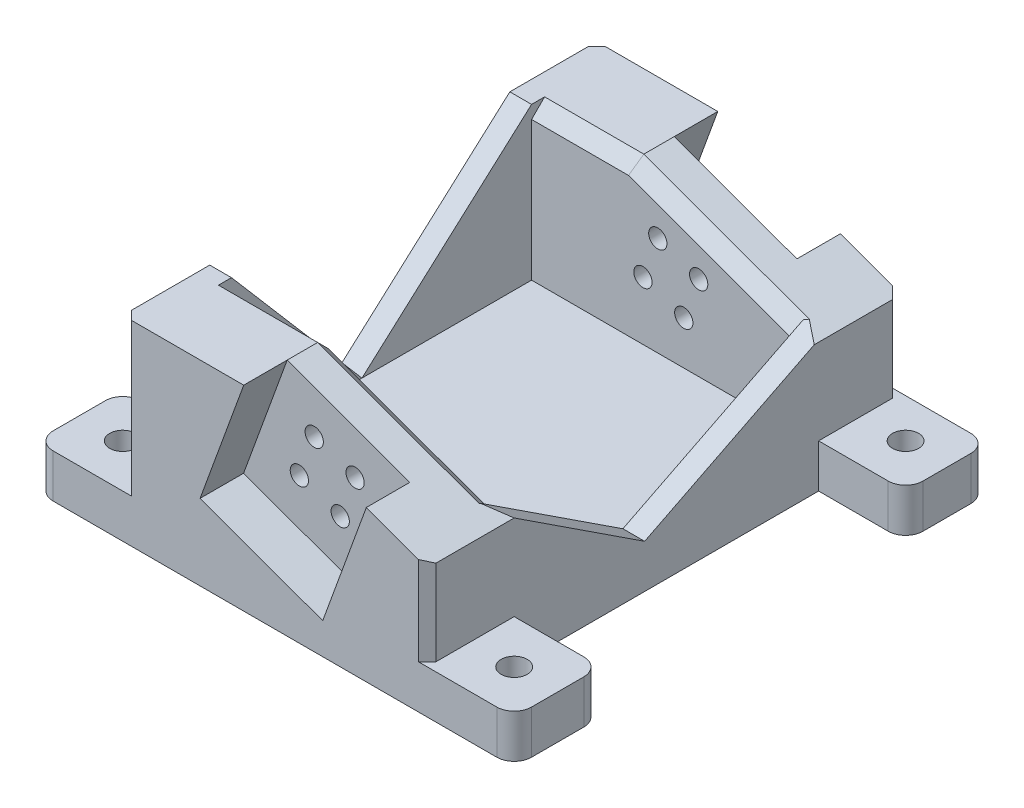
SolidWorks part; units mm, degrees
ref_plane "Спереди" through (0, 0, 0) normal (0, 0, 1) x (1, 0, 0)
ref_plane "Сверху" through (0, 0, 0) normal (0, 1, 0) x (1, 0, 0)
ref_plane "Справа" through (0, 0, 0) normal (1, 0, 0) x (0, 0, -1)
sketch "Эскиз1" plane through (0, 0, 0) normal (0, 1, 0) x (1, 0, 0)
  line L0 (0, -40) -> (30, -40)
  line L2 (0, 49) -> (30, 49)
  line L3 (0, 49) -> (-40, 49)
  line L4 (-40, 49) -> (-40, 39)
  line L5 (-40, 39) -> (30, 39)
  line L6 (30, 39) -> (30, 49)
  line L7 (30, -40) -> (30, -30)
  line L8 (30, -30) -> (-40, -30)
  line L9 (-40, -30) -> (-40, -40)
  line L10 (-40, -40) -> (0, -40)
extrude "Бобышка-Вытянуть1" add sketch "Эскиз1" along normal blind 35
ref_plane "Плоскость1" through (0, 0, 40) normal (0, 0, 1) x (1, 0, 0)
sketch "Эскиз2" plane through (0, 0, 40) normal (0, 0, 1) x (1, 0, 0)
  circle A2 centre (0, 10) radius 2.1
  circle A5 centre (-9.3969, 13.4202) radius 2.1
  circle A6 centre (3.4202, 19.3969) radius 2.1
  circle A7 centre (-5.9767, 22.8171) radius 2.1
extrude "Вырез-Вытянуть1" cut sketch "Эскиз2" against normal through all both and the other way through all
sketch "Эскиз3" plane through (0, 0, 40) normal (0, 0, 1) x (1, 0, 0)
  line L0 (-40, 0) -> (-40, -10)
  line L1 (-40, -10) -> (30, -10)
  line L2 (30, -10) -> (30, 0)
  line L3 (-40, 0) -> (30, 0) construction
  line L4 (30, 0) -> (-40, 0)
extrude "Бобышка-Вытянуть2" add sketch "Эскиз3" against normal blind 89
sketch "Эскиз4" plane through (0, 0, 40) normal (0, 0, 1) x (1, 0, 0)
  line L0 (5.9767, -2.8171) -> (-22.2141, 7.4435)
  line L1 (-12.1843, 35) -> (-40, 35)
  line L2 (-40, 35) -> (-40, -10)
  line L4 (-22.2141, 7.4435) -> (-12.1843, 35)
  line L5 (-40, 35) -> (30, 35) construction
  line L8 (5.9767, -2.8171) -> (19.741, 35)
  line L10 (-40, -10) -> (30, -10)
  line L11 (30, -10) -> (30, 35)
  line L12 (30, 35) -> (19.741, 35)
extrude "Бобышка-Вытянуть3" add sketch "Эскиз4" along normal blind 10
ref_plane "Плоскость2" through (0, 0, -49) normal (0, 0, -1) x (-1, 0, 0)
sketch "Эскиз5" plane through (0, 0, -49) normal (0, 0, -1) x (-1, 0, 0)
  line L0 (-30, 35) -> (-30, -10)
  line L1 (-30, -10) -> (40, -10)
  line L2 (40, -10) -> (40, 35)
  line L3 (40, 35) -> (12.1843, 35)
  line L4 (12.1843, 35) -> (22.2141, 7.4435)
  line L5 (22.2141, 7.4435) -> (-5.9767, -2.8171)
  line L6 (-5.9767, -2.8171) -> (-19.741, 35)
  line L7 (-19.741, 35) -> (-30, 35)
extrude "Бобышка-Вытянуть4" add sketch "Эскиз5" along normal blind 10
ref_plane "Плоскость3" through (-40, 0, 0) normal (-1, 0, 0) x (0, 0, 1)
sketch "Эскиз6" plane through (-40, 0, 0) normal (-1, 0, 0) x (0, 0, 1)
  line L0 (-39, 35) -> (-39, 0)
  line L1 (-39, 0) -> (0, 0)
  line L2 (0, 0) -> (-39, 35)
  line L3 (0, 0) -> (30, 0)
  line L4 (30, 0) -> (30, 35)
  line L5 (30, 35) -> (0, 0)
ref_plane "Плоскость4" through (30, 0, 0) normal (1, 0, 0) x (0, 0, -1)
ref_plane "Плоскость5" through (0, -10, 0) normal (0, -1, 0) x (-1, 0, 0)
sketch "Эскиз8" plane through (0, -10, 0) normal (0, -1, 0) x (-1, 0, 0)
  line L0 (-30, 59) -> (-50, 59)
  line L1 (-50, 59) -> (-50, 40)
  line L2 (-50, 40) -> (-30, 40)
  line L3 (-30, 39) -> (-30, 59) construction
  line L4 (-30, 40) -> (-30, 59)
  line L5 (-30, -50) -> (-50, -50)
  line L6 (-50, -50) -> (-50, -30)
  line L7 (-50, -30) -> (-30, -30)
  line L8 (-30, -50) -> (-30, -30) construction
  line L9 (-30, -30) -> (-30, -50)
  line L10 (40, 59) -> (60, 59)
  line L11 (60, 59) -> (60, 40)
  line L12 (60, 40) -> (40, 40)
  line L13 (40, 59) -> (40, 39) construction
  line L14 (40, 40) -> (40, 59)
  line L16 (60, -50) -> (60, -30)
  line L17 (60, -30) -> (40, -30)
  line L18 (40, -30) -> (40, -50) construction
  line L19 (40, -30) -> (40, -50)
  line L20 (60, -50) -> (40, -50)
  circle A0 centre (-40, 50) radius 3
  circle A2 centre (-40, -40) radius 3
  circle A3 centre (50, -40) radius 3
  circle A4 centre (50, 50) radius 3
extrude "Бобышка-Вытянуть9" add sketch "Эскиз8" against normal blind 10
extrude "Бобышка-Вытянуть10" add sketch "Эскиз6" against normal blind 5 contours L1 L2 L0 | L4 L5 L3
ref_plane "Плоскость6" through (30, 0, 0) normal (1, 0, 0) x (0, 0, -1)
ref_plane "Плоскость7" through (0, 0, 50) normal (0, 0, 1) x (1, 0, 0)
sketch "Эскиз10" plane through (0, 0, 50) normal (0, 0, 1) x (1, 0, 0)
  line L0 (30, 19.6462) -> (-12.1843, 35)
  line L1 (30, 35) -> (-12.1843, 35)
  line L2 (30, 35) -> (30, 19.6462)
  line L3 (30, -10) -> (30, 35) construction
extrude "Вырез-Вытянуть2" cut sketch "Эскиз10" against normal through all both and the other way through all
sketch "Эскиз9" plane through (30, 0, 0) normal (1, 0, 0) x (0, 0, -1)
  line L1 (-30, 0) -> (0, 0)
  line L2 (0, 0) -> (39, 0)
  line L6 (0, 0) -> (-30, 19.6462)
  line L7 (-30, 19.6462) -> (-30, 0)
  line L8 (0, 0) -> (39, 19.6462)
  line L9 (39, 19.6462) -> (39, 0)
extrude "Бобышка-Вытянуть12" add sketch "Эскиз9" against normal blind 5 contours L9 L8 L2 | L6 L7 L1
fillet "Скругление1" radius 4 4 edges at (50, -5, 50) (50, -5, -59) (-60, -5, 50) (-60, -5, -59)
fillet "Скругление2" radius 4 4 edges at (-60, -5, -40) (-60, -5, 30) (50, -5, 30) (50, -5, -40)
chamfer "Фаска3" distance 3 angle 45 4 edges at (-23.5921, 35, -39) (8.9079, 27.3231, -39) (-23.5921, 35, 30) (8.9079, 27.3231, 30)
chamfer "Фаска4" distance 2 angle 45 4 edges at (-40, 17.5, 50) (30, 9.8231, 50) (-40, 17.5, -59) (30, 9.8231, -59)
